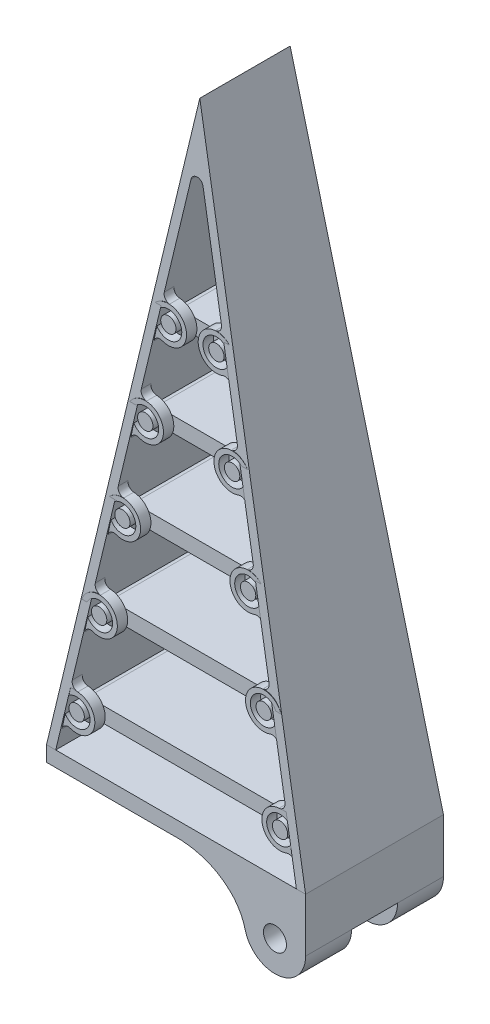
SolidWorks part; units mm, degrees
ref_plane "Ebene vorne" through (0, 0, 0) normal (0, 0, 1) x (1, 0, 0)
ref_plane "Ebene oben" through (0, 0, 0) normal (0, 1, 0) x (1, 0, 0)
ref_plane "Ebene rechts" through (0, 0, 0) normal (1, 0, 0) x (0, 0, -1)
ref_plane "Ebene7" through (0, 0, 9) normal (0, 0, 1) x (1, 0, 0)
ref_plane "Ebene8" through (17, 0, 0) normal (1, 0, 0) x (0, 0, -1)
sketch "Skizze1" plane through (0, 0, 0) normal (0, 0, 1) x (1, 0, 0)
  line L0 (0, 0) -> (16.9111, -80)
  line L1 (16.9111, -80) -> (15.7111, -80)
  line L2 (15.7111, -80) -> (0, -5.6767)
  line L3 (0, -5.6767) -> (-15.7111, -80)
  line L4 (-15.7111, -80) -> (-16.9111, -80)
  line L5 (-16.9111, -80) -> (0, 0)
  point P2 (-16.3111, -80)
  dimension "D1" = 1.2
  dimension "D2" = 1.2
  dimension "D3" = 23.872
  dimension "D4" = 80
extrude "Aufsatz-Linear austragen4" add sketch "Skizze1" along normal blind 18
sketch "Skizze11" plane through (17, 0, 0) normal (1, 0, 0) x (0, 0, -1)
  line L0 (-18, -80) -> (-14.9, 0)
  line L1 (-18, 0) -> (0, 0) construction
  line L2 (-14.9, 0) -> (-18, 0)
  line L3 (-18, 0) -> (-18, -80)
  line L4 (0, -80) -> (-3.1, 0)
  line L5 (-3.1, 0) -> (0, 0)
  line L6 (0, 0) -> (0, -80)
  dimension "D1" = 3.1
  dimension "D2" = 3.1
extrude "Schnitt-Linear austragen1" cut sketch "Skizze11" against normal through all
sketch "Skizze6" plane through (0, 0, 9) normal (0, 0, 1) x (1, 0, 0)
  line L1 (0, -5.6767) -> (-15.7111, -80) construction
  line L2 (15.7111, -80) -> (0, -5.6767) construction
  line L8 (3.1325, -25.6767) -> (-3.1325, -25.6767)
  line L11 (-3.1325, -27.6767) -> (3.1325, -27.6767)
  arc A0 (-3.1325, -25.6767) -> (-3.1325, -27.6767) centre (-3.1325, -26.6767) ccw
  arc A1 (3.1325, -25.6767) -> (3.1325, -27.6767) centre (3.1325, -26.6767) cw
  point P4 (-4.1325, -26.6767)
  point P9 (4.1325, -26.6767)
  dimension "D3" = 0.3
  dimension "D1" = 20
  dimension "D2" = 2
  dimension "D4" = 0.3
extrude "Aufsatz-Linear austragen5" add sketch "Skizze6" along normal blind 5.37 and the other way blind 5.37
sketch "Skizze7" plane through (0, 0, 9) normal (0, 0, 1) x (1, 0, 0)
  line L9 (5.6692, -37.6767) -> (-5.6692, -37.6767)
  line L12 (-5.6692, -39.6767) -> (5.6692, -39.6767)
  line L13 (-3.1325, -27.6767) -> (3.1325, -27.6767) construction
  line L14 (0, -5.6767) -> (-15.7111, -80) construction
  line L15 (15.7111, -80) -> (0, -5.6767) construction
  arc A0 (-5.6692, -37.6767) -> (-5.6692, -39.6767) centre (-5.6692, -38.6767) ccw
  arc A1 (5.6692, -37.6767) -> (5.6692, -39.6767) centre (5.6692, -38.6767) cw
  point P3 (-6.6692, -38.6767)
  point P10 (6.6692, -38.6767)
  dimension "D3" = 0.3
  dimension "D1" = 10
  dimension "D2" = 2
  dimension "D4" = 0.3
extrude "Aufsatz-Linear austragen6" add sketch "Skizze7" along normal blind 5.85 and the other way blind 5.85
sketch "Skizze8" plane through (0, 0, 9) normal (0, 0, 1) x (1, 0, 0)
  line L9 (8.2059, -49.6767) -> (-8.2059, -49.6767)
  line L12 (-8.2059, -51.6767) -> (8.2059, -51.6767)
  line L13 (-5.6692, -39.6767) -> (5.6692, -39.6767) construction
  line L14 (0, -5.6767) -> (-15.7111, -80) construction
  line L15 (15.7111, -80) -> (0, -5.6767) construction
  arc A0 (-8.2059, -49.6767) -> (-8.2059, -51.6767) centre (-8.2059, -50.6767) ccw
  arc A1 (8.2059, -49.6767) -> (8.2059, -51.6767) centre (8.2059, -50.6767) cw
  point P6 (-9.2059, -50.6767)
  point P11 (9.2059, -50.6767)
  dimension "D3" = 0.3
  dimension "D1" = 10
  dimension "D2" = 2
  dimension "D4" = 0.3
extrude "Aufsatz-Linear austragen7" add sketch "Skizze8" along normal blind 6.3 and the other way blind 6.3
sketch "Skizze9" plane through (0, 0, 9) normal (0, 0, 1) x (1, 0, 0)
  line L9 (10.7426, -61.6767) -> (-10.7426, -61.6767)
  line L12 (-10.7426, -63.6767) -> (10.7426, -63.6767)
  line L13 (-8.2059, -51.6767) -> (8.2059, -51.6767) construction
  line L14 (0, -5.6767) -> (-15.7111, -80) construction
  line L15 (15.7111, -80) -> (0, -5.6767) construction
  arc A0 (-10.7426, -61.6767) -> (-10.7426, -63.6767) centre (-10.7426, -62.6767) ccw
  arc A1 (10.7426, -61.6767) -> (10.7426, -63.6767) centre (10.7426, -62.6767) cw
  point P3 (-11.7426, -62.6767)
  point P10 (11.7426, -62.6767)
  dimension "D3" = 0.3
  dimension "D1" = 10
  dimension "D2" = 2
  dimension "D4" = 0.3
extrude "Aufsatz-Linear austragen8" add sketch "Skizze9" along normal blind 6.8 and the other way blind 6.8
sketch "Skizze10" plane through (0, 0, 9) normal (0, 0, 1) x (1, 0, 0)
  line L9 (13.2792, -73.6767) -> (-13.2792, -73.6767)
  line L12 (-13.2792, -75.6767) -> (13.2792, -75.6767)
  line L13 (-10.7426, -63.6767) -> (10.7426, -63.6767) construction
  line L14 (0, -5.6767) -> (-15.7111, -80) construction
  line L15 (15.7111, -80) -> (0, -5.6767) construction
  arc A0 (-13.2792, -73.6767) -> (-13.2792, -75.6767) centre (-13.2792, -74.6767) ccw
  arc A1 (13.2792, -73.6767) -> (13.2792, -75.6767) centre (13.2792, -74.6767) cw
  point P3 (-14.2792, -74.6767)
  point P10 (14.2792, -74.6767)
  dimension "D3" = 0.3
  dimension "D1" = 10
  dimension "D2" = 2
  dimension "D4" = 0.3
extrude "Aufsatz-Linear austragen9" add sketch "Skizze10" along normal blind 7.2 and the other way blind 7.2
sketch "Skizze13" plane through (0, 0, 14.37) normal (0, 0, 1) x (1, 0, 0)
  circle A0 centre (-3.1325, -26.6767) radius 1
  circle A1 centre (3.1325, -26.6767) radius 1
  dimension "D1" = 2
  dimension "D2" = 2
extrude "Aufsatz-Linear austragen12" add sketch "Skizze13" along normal blind 1.5
sketch "Skizze15" plane through (0, 0, 15.3) normal (0, 0, 1) x (1, 0, 0)
  circle A0 centre (-8.2059, -50.6767) radius 1
  circle A1 centre (8.2059, -50.6767) radius 1
extrude "Aufsatz-Linear austragen14" add sketch "Skizze15" along normal blind 1.5
sketch "Skizze14" plane through (0, 0, 14.85) normal (0, 0, 1) x (1, 0, 0)
  circle A0 centre (-5.6692, -38.6767) radius 1
  circle A1 centre (5.6692, -38.6767) radius 1
extrude "Aufsatz-Linear austragen13" add sketch "Skizze14" along normal blind 1.5
sketch "Skizze16" plane through (0, 0, 15.8) normal (0, 0, 1) x (1, 0, 0)
  circle A0 centre (-10.7426, -62.6767) radius 1
  circle A1 centre (10.7426, -62.6767) radius 1
extrude "Aufsatz-Linear austragen15" add sketch "Skizze16" along normal blind 1.5
sketch "Skizze17" plane through (0, 0, 16.2) normal (0, 0, 1) x (1, 0, 0)
  circle A0 centre (-13.2792, -74.6767) radius 1
  circle A1 centre (13.2792, -74.6767) radius 1
extrude "Aufsatz-Linear austragen16" add sketch "Skizze17" along normal blind 1.5
sketch "Skizze18" plane through (0, 0, 3.63) normal (0, 0, -1) x (-1, 0, 0)
  circle A0 centre (-3.1325, -26.6767) radius 1
  circle A1 centre (3.1325, -26.6767) radius 1
extrude "Aufsatz-Linear austragen17" add sketch "Skizze18" along normal blind 1.5
sketch "Skizze19" plane through (0, 0, 3.15) normal (0, 0, -1) x (-1, 0, 0)
  circle A0 centre (-5.6692, -38.6767) radius 1
  circle A1 centre (5.6692, -38.6767) radius 1
extrude "Aufsatz-Linear austragen18" add sketch "Skizze19" along normal blind 1.5
sketch "Skizze20" plane through (0, 0, 2.7) normal (0, 0, -1) x (-1, 0, 0)
  circle A0 centre (-8.2059, -50.6767) radius 1
  circle A1 centre (8.2059, -50.6767) radius 1
extrude "Aufsatz-Linear austragen19" add sketch "Skizze20" along normal blind 1.5
sketch "Skizze21" plane through (0, 0, 2.2) normal (0, 0, -1) x (-1, 0, 0)
  circle A0 centre (-10.7426, -62.6767) radius 1
  circle A1 centre (10.7426, -62.6767) radius 1
extrude "Aufsatz-Linear austragen20" add sketch "Skizze21" along normal blind 1.5
sketch "Skizze22" plane through (0, 0, 1.8) normal (0, 0, -1) x (-1, 0, 0)
  circle A0 centre (-13.2792, -74.6767) radius 1
  circle A1 centre (13.2792, -74.6767) radius 1
extrude "Aufsatz-Linear austragen21" add sketch "Skizze22" along normal blind 1.5
sketch "Skizze24" plane through (0, 0, 15.87) normal (0, 0, 1) x (1, 0, 0)
  circle A0 centre (-3.1325, -26.6767) radius 1.75
  circle A1 centre (-3.1325, -26.6767) radius 2.375
  circle A2 centre (3.1325, -26.6767) radius 1.75
  circle A3 centre (3.1325, -26.6767) radius 2.375
  dimension "D1" = 3.5
  dimension "D2" = 4.75
  dimension "D3" = 3.5
  dimension "D4" = 4.75
extrude "Aufsatz-Linear austragen22" add sketch "Skizze24" against normal blind 1.35
sketch "Skizze25" plane through (0, 0, 16.35) normal (0, 0, 1) x (1, 0, 0)
  circle A0 centre (-5.6692, -38.6767) radius 1.75
  circle A1 centre (-5.6692, -38.6767) radius 2.375
  circle A2 centre (5.6692, -38.6767) radius 1.75
  circle A3 centre (5.6692, -38.6767) radius 2.375
  dimension "D1" = 3.5
  dimension "D2" = 4.75
  dimension "D3" = 3.5
  dimension "D4" = 4.75
extrude "Aufsatz-Linear austragen23" add sketch "Skizze25" against normal blind 1.35
sketch "Skizze26" plane through (0, 0, 16.8) normal (0, 0, 1) x (1, 0, 0)
  circle A0 centre (-8.2059, -50.6767) radius 1.75
  circle A1 centre (-8.2059, -50.6767) radius 2.375
  circle A2 centre (8.2059, -50.6767) radius 1.75
  circle A3 centre (8.2059, -50.6767) radius 2.375
  dimension "D1" = 3.5
  dimension "D2" = 4.75
  dimension "D3" = 3.5
  dimension "D4" = 4.75
extrude "Aufsatz-Linear austragen24" add sketch "Skizze26" against normal blind 1.35
sketch "Skizze27" plane through (0, 0, 17.3) normal (0, 0, 1) x (1, 0, 0)
  circle A0 centre (-10.7426, -62.6767) radius 1.75
  circle A1 centre (-10.7426, -62.6767) radius 2.375
  circle A2 centre (10.7426, -62.6767) radius 1.75
  circle A3 centre (10.7426, -62.6767) radius 2.375
  dimension "D1" = 3.5
  dimension "D2" = 4.75
  dimension "D3" = 3.5
  dimension "D4" = 4.75
extrude "Aufsatz-Linear austragen25" add sketch "Skizze27" against normal blind 1.35
sketch "Skizze28" plane through (0, 0, 17.7) normal (0, 0, 1) x (1, 0, 0)
  circle A0 centre (-13.2792, -74.6767) radius 1.75
  circle A1 centre (-13.2792, -74.6767) radius 2.375
  circle A2 centre (13.2792, -74.6767) radius 1.75
  circle A3 centre (13.2792, -74.6767) radius 2.375
  dimension "D1" = 3.5
  dimension "D2" = 4.75
  dimension "D3" = 3.5
  dimension "D4" = 4.75
extrude "Aufsatz-Linear austragen26" add sketch "Skizze28" against normal blind 1.35
sketch "Skizze29" plane through (0, 0, 2.13) normal (0, 0, -1) x (-1, 0, 0)
  circle A0 centre (-3.1325, -26.6767) radius 1.75
  circle A1 centre (-3.1325, -26.6767) radius 2.375
  circle A2 centre (3.1325, -26.6767) radius 1.75
  circle A3 centre (3.1325, -26.6767) radius 2.375
extrude "Aufsatz-Linear austragen27" add sketch "Skizze29" against normal blind 1.35
sketch "Skizze30" plane through (0, 0, 1.65) normal (0, 0, -1) x (-1, 0, 0)
  circle A0 centre (-5.6692, -38.6767) radius 1.75
  circle A1 centre (-5.6692, -38.6767) radius 2.375
  circle A2 centre (5.6692, -38.6767) radius 1.75
  circle A3 centre (5.6692, -38.6767) radius 2.375
extrude "Aufsatz-Linear austragen28" add sketch "Skizze30" against normal blind 1.35
sketch "Skizze31" plane through (0, 0, 1.2) normal (0, 0, -1) x (-1, 0, 0)
  circle A0 centre (-8.2059, -50.6767) radius 1.75
  circle A1 centre (-8.2059, -50.6767) radius 2.375
  circle A2 centre (8.2059, -50.6767) radius 1.75
  circle A3 centre (8.2059, -50.6767) radius 2.375
extrude "Aufsatz-Linear austragen29" add sketch "Skizze31" against normal blind 1.35
sketch "Skizze32" plane through (0, 0, 0.7) normal (0, 0, -1) x (-1, 0, 0)
  circle A0 centre (-10.7426, -62.6767) radius 1.75
  circle A1 centre (-10.7426, -62.6767) radius 2.375
  circle A2 centre (10.7426, -62.6767) radius 1.75
  circle A3 centre (10.7426, -62.6767) radius 2.375
extrude "Aufsatz-Linear austragen30" add sketch "Skizze32" against normal blind 1.35
sketch "Skizze33" plane through (0, 0, 0.3) normal (0, 0, -1) x (-1, 0, 0)
  circle A0 centre (-13.2792, -74.6767) radius 1.75
  circle A1 centre (-13.2792, -74.6767) radius 2.375
  circle A2 centre (13.2792, -74.6767) radius 1.75
  circle A3 centre (13.2792, -74.6767) radius 2.375
extrude "Aufsatz-Linear austragen31" add sketch "Skizze33" against normal blind 1.35
fillet "Verrundung1" radius 0.8 1 edges at (0, -5.6767, 9)
fillet "Verrundung2" radius 0.8 40 edges at (12.4073, -64.3707, 16.625) (9.8706, -52.3707, 16.125) (7.3339, -40.3707, 15.675) (4.7973, -28.3707, 15.195) (-4.7973, -28.3707, 15.195) (-7.3339, -40.3707, 15.675) (-9.8706, -52.3707, 16.125) (-12.4073, -64.3707, 16.625) (-14.9439, -76.3707, 17.025) (14.9439, -76.3707, 17.025) (14.116, -72.454, 17.025) (-14.116, -72.454, 17.025) (-11.5793, -60.454, 16.5963) (11.5793, -60.454, 16.5963) (9.0427, -48.454, 16.1138) (-9.0427, -48.454, 16.1138) (-6.506, -36.454, 15.6563) (6.506, -36.454, 15.6563) (3.9693, -24.454, 15.1838) (-3.9693, -24.454, 15.1838) (-7.3339, -40.3707, 2.325) (-4.7973, -28.3707, 2.805) (-3.9693, -24.454, 2.8162) (-6.506, -36.454, 2.3437) (-9.0427, -48.454, 1.8862) (-9.8706, -52.3707, 1.875) (-12.4073, -64.3707, 1.375) (-11.5793, -60.454, 1.4037) (-14.116, -72.454, 0.975) (-14.9439, -76.3707, 0.975) (14.9439, -76.3707, 0.975) (14.116, -72.454, 0.975) (12.4073, -64.3707, 1.375) (11.5793, -60.454, 1.4037) (9.8706, -52.3707, 1.875) (9.0427, -48.454, 1.8862) (7.3339, -40.3707, 2.325) (6.506, -36.454, 2.3437) (4.7973, -28.3707, 2.805) (3.9693, -24.454, 2.8162)
sketch "Skizze37" plane through (0, -80, 0) normal (0, -1, 0) x (1, 0, 0)
  line L0 (-16.9111, 0) -> (-15.7111, 0)
  line L1 (-15.7111, 0) -> (16.9111, 0)
  line L2 (16.9111, 0) -> (16.9111, 18)
  line L3 (16.9111, 18) -> (-16.9111, 18)
  line L4 (-16.9111, 18) -> (-16.9111, 0)
extrude "Aufsatz-Linear austragen32" add sketch "Skizze37" along normal blind 2
sketch "Skizze38" plane through (0, 0, 18) normal (0, 0, 1) x (1, 0, 0)
  line L0 (16.9111, -82) -> (0.5278, -82)
  line L1 (16.9111, -82) -> (16.9111, -87)
  line L2 (16.9111, -82) -> (-16.9111, -82) construction
  line L3 (16.9111, -82) -> (16.9111, -80) construction
  circle A0 centre (12.9111, -87) radius 4
  circle A1 centre (12.9111, -87) radius 1.5
  spline S0 degree 2 poles (8.9111, -87) (6.2739, -82.291) (0.5278, -82) knots 0 0 0 1 1 1
  line M6 (-16.9111, -82) -> (16.9111, -82)
  dimension "D1" = 3
  dimension "D2" = 5
  dimension "D3" = 8
extrude "Aufsatz-Linear austragen34" add sketch "Skizze38" against normal blind 18 contours S0 A0 L1 M6 | A0 A1 region at (10.2012, -83.2525, 18) region at (12.9111, -90.8869, 18)
fillet "Verrundung3" radius 7 1 edges at (8.9111, -87, 9)
sketch "Skizze39" plane through (0, 0, 18) normal (0, 0, 1) x (1, 0, 0)
  circle A1 centre (12.9111, -87) radius 4
extrude "Schnitt-Linear austragen2" cut sketch "Skizze39" against normal blind 6 from offset 6 offset against normal yes
sketch "Skizze40" plane through (-16.9111, 0, 0) normal (-1, 0, 0) x (0, 0, 1)
  line L0 (6, -87.9656) -> (6, -82)
  line L1 (18, -82) -> (0, -82) construction
  line L2 (6, -87.9656) -> (12, -87.9656)
  line L3 (12, -87.9656) -> (12, -82)
  line L4 (0, -82) -> (18, -82) construction
  line L5 (12, -82) -> (6, -82)
extrude "Schnitt-Linear austragen3" cut sketch "Skizze40" against normal blind 33
